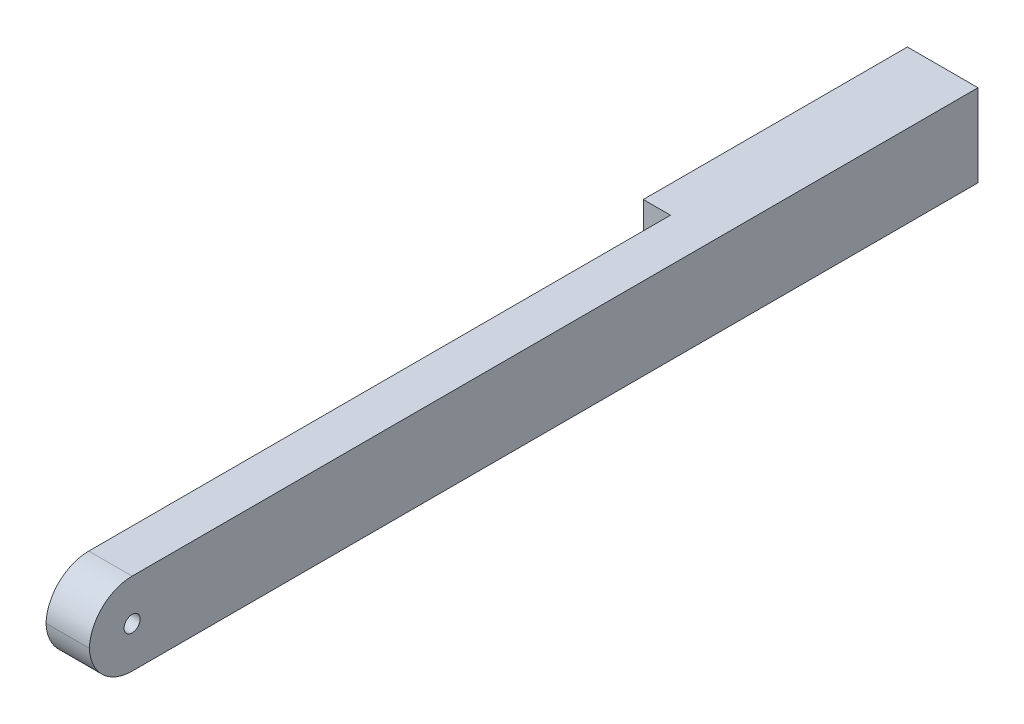
SolidWorks part; units mm, degrees
ref_plane "Ebene vorne" through (0, 0, 0) normal (0, 0, 1) x (1, 0, 0)
ref_plane "Ebene oben" through (0, 0, 0) normal (0, 1, 0) x (1, 0, 0)
ref_plane "Ebene rechts" through (0, 0, 0) normal (1, 0, 0) x (0, 0, -1)
sketch "Skizze1" plane through (0, 0, 0) normal (0, 0, 1) x (1, 0, 0)
  line L1 (-33, -38.5) -> (33, -38.5)
  line L2 (-33, -38.5) -> (-33, 38.5)
  line L3 (-33, 38.5) -> (33, 38.5)
  line L4 (33, -38.5) -> (33, 38.5)
  line L5 (-33, -38.5) -> (33, 38.5) construction
  line L6 (-33, 38.5) -> (33, -38.5) construction
  point P0 (0, 0)
  dimension "D1" = 77
  dimension "D2" = 66
extrude "Aufsatz-Linear austragen1" add sketch "Skizze1" along normal blind 831
sketch "Skizze2" plane through (0, 0, 0) normal (0, 0, -1) x (-1, 0, 0)
  line L0 (33, -20.5) -> (33, 8.5)
  line L1 (33, -20.5) -> (8, -20.5)
  line L2 (33, 8.5) -> (8, 8.5)
  line L3 (8, -20.5) -> (8, 8.5)
  line L4 (33, 38.5) -> (33, -38.5) construction
  line L5 (33, -38.5) -> (-33, -38.5) construction
  dimension "D1" = 18
  dimension "D2" = 25
  dimension "D3" = 29
extrude "Schnitt-Linear austragen1" cut sketch "Skizze2" against normal up to surface (831 mm away) up to face at (0, 0, 831)
sketch "Skizze3" plane through (-8, 0, 0) normal (-1, 0, 0) x (0, 0, 1)
  line L0 (18.367, -20.5) -> (10, -20.5)
  line L1 (0, -20.5) -> (3.0059, -12.2151)
  line L2 (3.0059, -12.2151) -> (5.361, -12.2151)
  line L3 (5.361, -12.2151) -> (8.367, -20.5)
  line L4 (831, -20.5) -> (0, -20.5) construction
  line L5 (8.367, -20.5) -> (0, -20.5)
  line L6 (10, -20.5) -> (13.0059, -12.2151)
  line L7 (13.0059, -12.2151) -> (15.361, -12.2151)
  line L8 (15.361, -12.2151) -> (18.367, -20.5)
  line L9 (28.367, -20.5) -> (20, -20.5)
  line L10 (20, -20.5) -> (23.0059, -12.2151)
  line L11 (23.0059, -12.2151) -> (25.361, -12.2151)
  line L12 (25.361, -12.2151) -> (28.367, -20.5)
  line L13 (38.367, -20.5) -> (30, -20.5)
  line L14 (30, -20.5) -> (33.0059, -12.2151)
  line L15 (33.0059, -12.2151) -> (35.361, -12.2151)
  line L16 (35.361, -12.2151) -> (38.367, -20.5)
  line L17 (48.367, -20.5) -> (40, -20.5)
  line L18 (40, -20.5) -> (43.0059, -12.2151)
  line L19 (43.0059, -12.2151) -> (45.361, -12.2151)
  line L20 (45.361, -12.2151) -> (48.367, -20.5)
  line L21 (58.367, -20.5) -> (50, -20.5)
  line L22 (50, -20.5) -> (53.0059, -12.2151)
  line L23 (53.0059, -12.2151) -> (55.361, -12.2151)
  line L24 (55.361, -12.2151) -> (58.367, -20.5)
  line L25 (68.367, -20.5) -> (60, -20.5)
  line L26 (60, -20.5) -> (63.0059, -12.2151)
  line L27 (63.0059, -12.2151) -> (65.361, -12.2151)
  line L28 (65.361, -12.2151) -> (68.367, -20.5)
  line L29 (78.367, -20.5) -> (70, -20.5)
  line L30 (70, -20.5) -> (73.0059, -12.2151)
  line L31 (73.0059, -12.2151) -> (75.361, -12.2151)
  line L32 (75.361, -12.2151) -> (78.367, -20.5)
  line L33 (88.367, -20.5) -> (80, -20.5)
  line L34 (80, -20.5) -> (83.0059, -12.2151)
  line L35 (83.0059, -12.2151) -> (85.361, -12.2151)
  line L36 (85.361, -12.2151) -> (88.367, -20.5)
  line L37 (98.367, -20.5) -> (90, -20.5)
  line L38 (90, -20.5) -> (93.0059, -12.2151)
  line L39 (93.0059, -12.2151) -> (95.361, -12.2151)
  line L40 (95.361, -12.2151) -> (98.367, -20.5)
  line L41 (108.367, -20.5) -> (100, -20.5)
  line L42 (100, -20.5) -> (103.0059, -12.2151)
  line L43 (103.0059, -12.2151) -> (105.361, -12.2151)
  line L44 (105.361, -12.2151) -> (108.367, -20.5)
  line L45 (118.367, -20.5) -> (110, -20.5)
  line L46 (110, -20.5) -> (113.0059, -12.2151)
  line L47 (113.0059, -12.2151) -> (115.361, -12.2151)
  line L48 (115.361, -12.2151) -> (118.367, -20.5)
  line L49 (128.367, -20.5) -> (120, -20.5)
  line L50 (120, -20.5) -> (123.0059, -12.2151)
  line L51 (123.0059, -12.2151) -> (125.361, -12.2151)
  line L52 (125.361, -12.2151) -> (128.367, -20.5)
  line L53 (138.367, -20.5) -> (130, -20.5)
  line L54 (130, -20.5) -> (133.0059, -12.2151)
  line L55 (133.0059, -12.2151) -> (135.361, -12.2151)
  line L56 (135.361, -12.2151) -> (138.367, -20.5)
  line L57 (148.367, -20.5) -> (140, -20.5)
  line L58 (140, -20.5) -> (143.0059, -12.2151)
  line L59 (143.0059, -12.2151) -> (145.361, -12.2151)
  line L60 (145.361, -12.2151) -> (148.367, -20.5)
  line L61 (158.367, -20.5) -> (150, -20.5)
  line L62 (150, -20.5) -> (153.0059, -12.2151)
  line L63 (153.0059, -12.2151) -> (155.361, -12.2151)
  line L64 (155.361, -12.2151) -> (158.367, -20.5)
  line L65 (168.367, -20.5) -> (160, -20.5)
  line L66 (160, -20.5) -> (163.0059, -12.2151)
  line L67 (163.0059, -12.2151) -> (165.361, -12.2151)
  line L68 (165.361, -12.2151) -> (168.367, -20.5)
  line L69 (178.367, -20.5) -> (170, -20.5)
  line L70 (170, -20.5) -> (173.0059, -12.2151)
  line L71 (173.0059, -12.2151) -> (175.361, -12.2151)
  line L72 (175.361, -12.2151) -> (178.367, -20.5)
  line L73 (188.367, -20.5) -> (180, -20.5)
  line L74 (180, -20.5) -> (183.0059, -12.2151)
  line L75 (183.0059, -12.2151) -> (185.361, -12.2151)
  line L76 (185.361, -12.2151) -> (188.367, -20.5)
  line L77 (198.367, -20.5) -> (190, -20.5)
  line L78 (190, -20.5) -> (193.0059, -12.2151)
  line L79 (193.0059, -12.2151) -> (195.361, -12.2151)
  line L80 (195.361, -12.2151) -> (198.367, -20.5)
  line L81 (208.367, -20.5) -> (200, -20.5)
  line L82 (200, -20.5) -> (203.0059, -12.2151)
  line L83 (203.0059, -12.2151) -> (205.361, -12.2151)
  line L84 (205.361, -12.2151) -> (208.367, -20.5)
  line L85 (218.367, -20.5) -> (210, -20.5)
  line L86 (210, -20.5) -> (213.0059, -12.2151)
  line L87 (213.0059, -12.2151) -> (215.361, -12.2151)
  line L88 (215.361, -12.2151) -> (218.367, -20.5)
  line L89 (228.367, -20.5) -> (220, -20.5)
  line L90 (220, -20.5) -> (223.0059, -12.2151)
  line L91 (223.0059, -12.2151) -> (225.361, -12.2151)
  line L92 (225.361, -12.2151) -> (228.367, -20.5)
  line L93 (238.367, -20.5) -> (230, -20.5)
  line L94 (230, -20.5) -> (233.0059, -12.2151)
  line L95 (233.0059, -12.2151) -> (235.361, -12.2151)
  line L96 (235.361, -12.2151) -> (238.367, -20.5)
  line L97 (248.367, -20.5) -> (240, -20.5)
  line L98 (240, -20.5) -> (243.0059, -12.2151)
  line L99 (243.0059, -12.2151) -> (245.361, -12.2151)
  line L100 (245.361, -12.2151) -> (248.367, -20.5)
  line L101 (258.367, -20.5) -> (250, -20.5)
  line L102 (250, -20.5) -> (253.0059, -12.2151)
  line L103 (253.0059, -12.2151) -> (255.361, -12.2151)
  line L104 (255.361, -12.2151) -> (258.367, -20.5)
  line L105 (268.367, -20.5) -> (260, -20.5)
  line L106 (260, -20.5) -> (263.0059, -12.2151)
  line L107 (263.0059, -12.2151) -> (265.361, -12.2151)
  line L108 (265.361, -12.2151) -> (268.367, -20.5)
  line L109 (278.367, -20.5) -> (270, -20.5)
  line L110 (270, -20.5) -> (273.0059, -12.2151)
  line L111 (273.0059, -12.2151) -> (275.361, -12.2151)
  line L112 (275.361, -12.2151) -> (278.367, -20.5)
  line L113 (288.367, -20.5) -> (280, -20.5)
  line L114 (280, -20.5) -> (283.0059, -12.2151)
  line L115 (283.0059, -12.2151) -> (285.361, -12.2151)
  line L116 (285.361, -12.2151) -> (288.367, -20.5)
  line L117 (298.367, -20.5) -> (290, -20.5)
  line L118 (290, -20.5) -> (293.0059, -12.2151)
  line L119 (293.0059, -12.2151) -> (295.361, -12.2151)
  line L120 (295.361, -12.2151) -> (298.367, -20.5)
  line L121 (308.367, -20.5) -> (300, -20.5)
  line L122 (300, -20.5) -> (303.0059, -12.2151)
  line L123 (303.0059, -12.2151) -> (305.361, -12.2151)
  line L124 (305.361, -12.2151) -> (308.367, -20.5)
  line L125 (318.367, -20.5) -> (310, -20.5)
  line L126 (310, -20.5) -> (313.0059, -12.2151)
  line L127 (313.0059, -12.2151) -> (315.361, -12.2151)
  line L128 (315.361, -12.2151) -> (318.367, -20.5)
  line L129 (328.367, -20.5) -> (320, -20.5)
  line L130 (320, -20.5) -> (323.0059, -12.2151)
  line L131 (323.0059, -12.2151) -> (325.361, -12.2151)
  line L132 (325.361, -12.2151) -> (328.367, -20.5)
  line L133 (338.367, -20.5) -> (330, -20.5)
  line L134 (330, -20.5) -> (333.0059, -12.2151)
  line L135 (333.0059, -12.2151) -> (335.361, -12.2151)
  line L136 (335.361, -12.2151) -> (338.367, -20.5)
  line L137 (348.367, -20.5) -> (340, -20.5)
  line L138 (340, -20.5) -> (343.0059, -12.2151)
  line L139 (343.0059, -12.2151) -> (345.361, -12.2151)
  line L140 (345.361, -12.2151) -> (348.367, -20.5)
  line L141 (358.367, -20.5) -> (350, -20.5)
  line L142 (350, -20.5) -> (353.0059, -12.2151)
  line L143 (353.0059, -12.2151) -> (355.361, -12.2151)
  line L144 (355.361, -12.2151) -> (358.367, -20.5)
  line L145 (368.367, -20.5) -> (360, -20.5)
  line L146 (360, -20.5) -> (363.0059, -12.2151)
  line L147 (363.0059, -12.2151) -> (365.361, -12.2151)
  line L148 (365.361, -12.2151) -> (368.367, -20.5)
  line L149 (378.367, -20.5) -> (370, -20.5)
  line L150 (370, -20.5) -> (373.0059, -12.2151)
  line L151 (373.0059, -12.2151) -> (375.361, -12.2151)
  line L152 (375.361, -12.2151) -> (378.367, -20.5)
  line L153 (388.367, -20.5) -> (380, -20.5)
  line L154 (380, -20.5) -> (383.0059, -12.2151)
  line L155 (383.0059, -12.2151) -> (385.361, -12.2151)
  line L156 (385.361, -12.2151) -> (388.367, -20.5)
  line L157 (398.367, -20.5) -> (390, -20.5)
  line L158 (390, -20.5) -> (393.0059, -12.2151)
  line L159 (393.0059, -12.2151) -> (395.361, -12.2151)
  line L160 (395.361, -12.2151) -> (398.367, -20.5)
  line L161 (408.367, -20.5) -> (400, -20.5)
  line L162 (400, -20.5) -> (403.0059, -12.2151)
  line L163 (403.0059, -12.2151) -> (405.361, -12.2151)
  line L164 (405.361, -12.2151) -> (408.367, -20.5)
  line L165 (418.367, -20.5) -> (410, -20.5)
  line L166 (410, -20.5) -> (413.0059, -12.2151)
  line L167 (413.0059, -12.2151) -> (415.361, -12.2151)
  line L168 (415.361, -12.2151) -> (418.367, -20.5)
  line L169 (428.367, -20.5) -> (420, -20.5)
  line L170 (420, -20.5) -> (423.0059, -12.2151)
  line L171 (423.0059, -12.2151) -> (425.361, -12.2151)
  line L172 (425.361, -12.2151) -> (428.367, -20.5)
  line L249 (8.367, -20.5) -> (18.367, -20.5) construction
  line L250 (438.367, -20.5) -> (430, -20.5) [skipped]
  line L251 (430, -20.5) -> (433.0059, -12.2151) [skipped]
  line L252 (433.0059, -12.2151) -> (435.361, -12.2151) [skipped]
  line L253 (435.361, -12.2151) -> (438.367, -20.5) [skipped]
  line L254 (448.367, -20.5) -> (440, -20.5) [skipped]
  line L255 (440, -20.5) -> (443.0059, -12.2151) [skipped]
  line L256 (443.0059, -12.2151) -> (445.361, -12.2151) [skipped]
  line L257 (445.361, -12.2151) -> (448.367, -20.5) [skipped]
  line L258 (458.367, -20.5) -> (450, -20.5) [skipped]
  line L259 (450, -20.5) -> (453.0059, -12.2151) [skipped]
  line L260 (453.0059, -12.2151) -> (455.361, -12.2151) [skipped]
  line L261 (455.361, -12.2151) -> (458.367, -20.5) [skipped]
  line L262 (468.367, -20.5) -> (460, -20.5) [skipped]
  line L263 (460, -20.5) -> (463.0059, -12.2151) [skipped]
  line L264 (463.0059, -12.2151) -> (465.361, -12.2151) [skipped]
  line L265 (465.361, -12.2151) -> (468.367, -20.5) [skipped]
  line L266 (478.367, -20.5) -> (470, -20.5) [skipped]
  line L267 (470, -20.5) -> (473.0059, -12.2151) [skipped]
  line L268 (473.0059, -12.2151) -> (475.361, -12.2151) [skipped]
  line L269 (475.361, -12.2151) -> (478.367, -20.5) [skipped]
  line L270 (488.367, -20.5) -> (480, -20.5) [skipped]
  line L271 (480, -20.5) -> (483.0059, -12.2151) [skipped]
  line L272 (483.0059, -12.2151) -> (485.361, -12.2151) [skipped]
  line L273 (485.361, -12.2151) -> (488.367, -20.5) [skipped]
  line L274 (498.367, -20.5) -> (490, -20.5) [skipped]
  line L275 (490, -20.5) -> (493.0059, -12.2151) [skipped]
  line L276 (493.0059, -12.2151) -> (495.361, -12.2151) [skipped]
  line L277 (495.361, -12.2151) -> (498.367, -20.5) [skipped]
  line L278 (508.367, -20.5) -> (500, -20.5) [skipped]
  line L279 (500, -20.5) -> (503.0059, -12.2151) [skipped]
  line L280 (503.0059, -12.2151) -> (505.361, -12.2151) [skipped]
  line L281 (505.361, -12.2151) -> (508.367, -20.5) [skipped]
  line L282 (518.367, -20.5) -> (510, -20.5) [skipped]
  line L283 (510, -20.5) -> (513.0059, -12.2151) [skipped]
  line L284 (513.0059, -12.2151) -> (515.361, -12.2151) [skipped]
  line L285 (515.361, -12.2151) -> (518.367, -20.5) [skipped]
  line L286 (528.367, -20.5) -> (520, -20.5) [skipped]
  line L287 (520, -20.5) -> (523.0059, -12.2151) [skipped]
  line L288 (523.0059, -12.2151) -> (525.361, -12.2151) [skipped]
  line L289 (525.361, -12.2151) -> (528.367, -20.5) [skipped]
  line L290 (538.367, -20.5) -> (530, -20.5) [skipped]
  line L291 (530, -20.5) -> (533.0059, -12.2151) [skipped]
  line L292 (533.0059, -12.2151) -> (535.361, -12.2151) [skipped]
  line L293 (535.361, -12.2151) -> (538.367, -20.5) [skipped]
  line L294 (548.367, -20.5) -> (540, -20.5) [skipped]
  line L295 (540, -20.5) -> (543.0059, -12.2151) [skipped]
  line L296 (543.0059, -12.2151) -> (545.361, -12.2151) [skipped]
  line L297 (545.361, -12.2151) -> (548.367, -20.5) [skipped]
  line L298 (558.367, -20.5) -> (550, -20.5) [skipped]
  line L299 (550, -20.5) -> (553.0059, -12.2151) [skipped]
  line L300 (553.0059, -12.2151) -> (555.361, -12.2151) [skipped]
  line L301 (555.361, -12.2151) -> (558.367, -20.5) [skipped]
  line L302 (568.367, -20.5) -> (560, -20.5) [skipped]
  line L303 (560, -20.5) -> (563.0059, -12.2151) [skipped]
  line L304 (563.0059, -12.2151) -> (565.361, -12.2151) [skipped]
  line L305 (565.361, -12.2151) -> (568.367, -20.5) [skipped]
  line L306 (578.367, -20.5) -> (570, -20.5) [skipped]
  line L307 (570, -20.5) -> (573.0059, -12.2151) [skipped]
  line L308 (573.0059, -12.2151) -> (575.361, -12.2151) [skipped]
  line L309 (575.361, -12.2151) -> (578.367, -20.5) [skipped]
  line L310 (588.367, -20.5) -> (580, -20.5) [skipped]
  line L311 (580, -20.5) -> (583.0059, -12.2151) [skipped]
  line L312 (583.0059, -12.2151) -> (585.361, -12.2151) [skipped]
  line L313 (585.361, -12.2151) -> (588.367, -20.5) [skipped]
  line L314 (598.367, -20.5) -> (590, -20.5) [skipped]
  line L315 (590, -20.5) -> (593.0059, -12.2151) [skipped]
  line L316 (593.0059, -12.2151) -> (595.361, -12.2151) [skipped]
  line L317 (595.361, -12.2151) -> (598.367, -20.5) [skipped]
  line L318 (608.367, -20.5) -> (600, -20.5) [skipped]
  line L319 (600, -20.5) -> (603.0059, -12.2151) [skipped]
  line L320 (603.0059, -12.2151) -> (605.361, -12.2151) [skipped]
  line L321 (605.361, -12.2151) -> (608.367, -20.5) [skipped]
  line L322 (618.367, -20.5) -> (610, -20.5) [skipped]
  line L323 (610, -20.5) -> (613.0059, -12.2151) [skipped]
  line L324 (613.0059, -12.2151) -> (615.361, -12.2151) [skipped]
  line L325 (615.361, -12.2151) -> (618.367, -20.5) [skipped]
  dimension "D1" = 10
  dimension "D2" = 62
extrude "Aufsatz-Linear austragen3" add sketch "Skizze3" along normal up to vertex (25 mm away) up to point (-33, -20.5, 0)
sketch "Skizze6" plane through (0, 0, 831) normal (0, 0, 1) x (1, 0, 0)
  line L0 (-33, 38.5) -> (-33, -38.5)
  line L1 (-33, 38.5) -> (-7.5521, 38.5)
  line L2 (-33, -38.5) -> (-7.5521, -38.5)
  line L3 (-7.5521, 38.5) -> (-7.5521, -38.5)
extrude "Schnitt-Linear austragen2" cut sketch "Skizze6" against normal blind 584
sketch "Skizze7" plane through (-7.5521, 0, 0) normal (-1, 0, 0) x (0, 0, 1)
  line L0 (831, -38.5) -> (831, 38.5) construction
  circle A0 centre (791, 0) radius 7.5
  point P4 (831, 0)
  dimension "D1" = 15
  dimension "D2" = 40
extrude "Schnitt-Linear austragen3" cut sketch "Skizze7" against normal up to surface (40.5521 mm away) up to face at (33, 0, 415.5)
fillet "Verrundung1" radius 40 2 edges at (12.7239, -38.5, 831) (12.7239, 38.5, 831)
move or copy body "Körper-Verschieben/Kopieren1" [suppressed] bodies to move or copy 108
